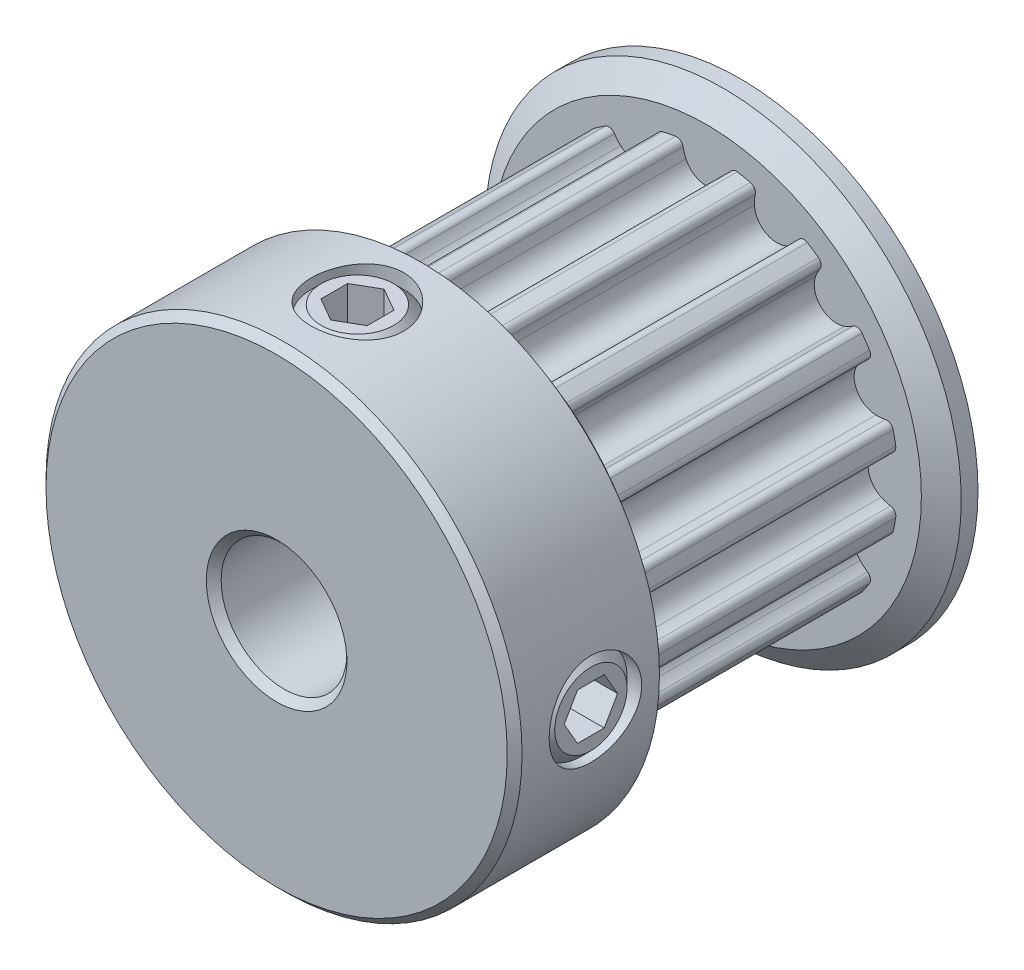
SolidWorks part; units mm, degrees
ref_plane "Front Plane" through (0, 0, 0) normal (0, 0, 1) x (1, 0, 0)
ref_plane "Top Plane" through (0, 0, 0) normal (0, 1, 0) x (1, 0, 0)
ref_plane "Right Plane" through (0, 0, 0) normal (1, 0, 0) x (0, 0, -1)
sketch "Sketch1" plane through (0, 0, 0) normal (0, 0, 1) x (1, 0, 0)
  line L1 (-2.553, 6.1245) -> (2.553, 6.1245) construction
  line L4 (0, 0) -> (0, 6.1245) construction
  line L5 (0, 6.1245) -> (0, 12.0714) construction
  line L6 (0, 7.6455) -> (2.9417, 7.0569) construction
  line L7 (2.9417, 7.0569) -> (3.8741, 6.6682) construction
  line L8 (2.9417, 7.0569) -> (2.553, 6.1245) construction
  line L9 (-2.9417, 7.0569) -> (-2.553, 6.1245) construction
  line L10 (-2.7951, 6.7052) -> (-3.7579, 9.015)
  line L11 (-3.7579, 9.015) -> (3.7579, 9.015)
  line L12 (3.7579, 9.015) -> (2.7951, 6.7052)
  circle A0 centre (0, 0) radius 7.6455 construction
  circle A1 centre (0, 0) radius 9.015 construction
  circle A2 centre (0, 0) radius 7.2645 construction
  arc A3 (-0.7739, 6.6229) -> (0.7739, 6.6229) centre (0, 6.9745) ccw
  arc A4 (-0.7739, 6.6229) -> (-0.8836, 6.9694) centre (0.61, 7.2516) cw
  arc A5 (-2.7951, 6.7052) -> (-1.1695, 7.1697) centre (0, 0) cw
  arc A6 (-0.8836, 6.9694) -> (-1.1695, 7.1697) centre (-1.1292, 6.923) ccw
  arc A7 (2.7951, 6.7052) -> (1.1695, 7.1697) centre (0, 0) ccw
  arc A8 (0.8836, 6.9694) -> (1.1695, 7.1697) centre (1.1292, 6.923) cw
  arc A9 (0.7739, 6.6229) -> (0.8836, 6.9694) centre (-0.61, 7.2516) ccw
  point P6 (0, 20.9083)
  point P11 (0, 7.6455)
  point P13 (0, 9.015)
  point P14 (0, 7.2645)
  dimension "D1" = 8.8369
  dimension "D2" = 4.4259
sketch "Sketch2" plane through (0, 0, 0) normal (1, 0, 0) x (0, 0, -1)
  line L0 (-8.775, 2.3812) -> (8.775, 2.3812)
  line L1 (-8.775, 2.3812) -> (-8.775, 9.015)
  line L2 (-3.29, 9.015) -> (-8.775, 9.015)
  line L3 (-3.925, 2.3813) -> (-3.925, 9.015) construction
  line L4 (-3.925, 9.015) -> (-2.655, 9.015) construction
  line L5 (-2.655, 9.015) -> (-2.655, 7.2645) construction
  line L6 (-2.655, 7.2645) -> (7.505, 7.2645)
  line L7 (7.505, 7.2645) -> (7.505, 9.015) construction
  line L8 (7.505, 9.015) -> (8.775, 9.015) construction
  line L9 (8.775, 9.015) -> (8.775, 2.3812)
  line L10 (-8.775, 0) -> (8.775, 0) construction
  line L11 (8.14, 9.015) -> (7.505, 8.1398)
  line L12 (-2.655, 8.1398) -> (-3.29, 9.015)
  line L14 (-2.655, 8.1398) -> (-2.655, 7.2645)
  line L15 (7.505, 7.2645) -> (7.505, 8.1398)
  line L16 (8.14, 9.015) -> (8.775, 9.015)
  arc A0 (-2.655, 8.1398) -> (-3.29, 9.015) centre (-3.5757, 8.1398) ccw construction
  arc A1 (7.505, 8.1398) -> (8.14, 9.015) centre (8.4257, 8.1398) cw construction
  point P12 (-2.655, 8.1398)
  point P14 (-3.29, 9.015)
  point P20 (7.505, 8.1398)
  point P21 (8.14, 9.015)
  point P25 (7.505, 0)
  point P26 (-2.655, 0)
  dimension "OA" = 17.55
  dimension "Bore" = 4.7625
  dimension "Outside Width" = 11.43
  dimension "Inside Width" = 10.16
revolve "Revolve1" add sketch "Sketch2" angle 360 mid plane about L10
sketch "Sketch3" plane through (0, 0, 0) normal (0, 0, 1) x (1, 0, 0)
  line L6 (3.7579, 9.015) -> (-3.7579, 9.015)
  line L7 (2.7951, 6.7052) -> (3.7579, 9.015)
  line L8 (-3.7579, 9.015) -> (-2.7951, 6.7052)
  line L9 (3.7579, 9.015) -> (-3.7579, 9.015)
  line L10 (2.7951, 6.7052) -> (3.7579, 9.015)
  line L11 (-3.7579, 9.015) -> (-2.7951, 6.7052)
  arc A8 (2.7951, 6.7052) -> (1.1695, 7.1697) centre (0, 0) ccw
  arc A9 (1.1695, 7.1697) -> (0.8836, 6.9694) centre (1.1292, 6.923) ccw
  arc A10 (0.7739, 6.6229) -> (0.8836, 6.9694) centre (-0.61, 7.2516) ccw
  arc A11 (-0.7739, 6.6229) -> (0.7739, 6.6229) centre (0, 6.9745) ccw
  arc A12 (-0.8836, 6.9694) -> (-0.7739, 6.6229) centre (0.61, 7.2516) ccw
  arc A13 (-0.8836, 6.9694) -> (-1.1695, 7.1697) centre (-1.1292, 6.923) ccw
  arc A14 (-1.1695, 7.1697) -> (-2.7951, 6.7052) centre (0, 0) ccw
  arc A15 (2.7951, 6.7052) -> (1.1695, 7.1697) centre (0, 0) ccw
  arc A16 (1.1695, 7.1697) -> (0.8836, 6.9694) centre (1.1292, 6.923) ccw
  arc A17 (0.7739, 6.6229) -> (0.8836, 6.9694) centre (-0.61, 7.2516) ccw
  arc A18 (-0.7739, 6.6229) -> (0.7739, 6.6229) centre (0, 6.9745) ccw
  arc A19 (-0.8836, 6.9694) -> (-0.7739, 6.6229) centre (0.61, 7.2516) ccw
  arc A20 (-0.8836, 6.9694) -> (-1.1695, 7.1697) centre (-1.1292, 6.923) ccw
  arc A21 (-1.1695, 7.1697) -> (-2.7951, 6.7052) centre (0, 0) ccw
  dimension "D1" = 0
extrude "Cut-Extrude1" cut sketch "Sketch3" against normal up to vertex (7.505 mm away) from vertex up to point (0, 7.2645, -7.505) starting at point (0, 7.2645, 2.655)
pattern_circular "CirPattern1" count 16 over 360 about axis through (0, 0, 8.775) along (0, 0, 1) of "Cut-Extrude1"
sketch "Sketch4" plane through (0, 0, 0) normal (1, 0, 0) x (0, -1, 0)
  line L0 (0, -2.655) -> (0, -8.775) construction
  line L1 (-2.3812, -8.775) -> (2.3812, -8.775) construction
  line L2 (8.1398, -2.655) -> (-8.1398, -2.655) construction
  circle A0 centre (0, -5.715) radius 1.7526
extrude "Cut-Extrude2" cut sketch "Sketch4" along normal through all
ref_plane "Plane1" through (0, 0, 5.715) normal (0, 0, 1) x (1, 0, 0)
sketch "Sketch5" plane through (0, 0, 5.715) normal (0, 0, 1) x (1, 0, 0)
  line L0 (0, 0) -> (0, 9.015) construction
  line L1 (2.3812, -1.3716) -> (2.3812, 0)
  line L2 (2.7622, -1.7526) -> (8.462, -1.7526)
  line L3 (2.3812, 0) -> (9.015, 0) construction
  line L4 (2.3812, 0) -> (8.843, 0)
  line L5 (8.843, 0) -> (8.843, -1.3716)
  line L6 (2.7622, -1.7526) -> (2.3812, -1.3716)
  line L7 (8.843, -1.3716) -> (8.462, -1.7526)
  circle A0 centre (0, 0) radius 9.015 construction
  circle A1 centre (0, 0) radius 2.3812 construction
  point P2 (2.3812, -1.7526)
  point P11 (8.843, -1.7526)
revolve "Revolve2" add sketch "Sketch5" angle 360 mid plane about L4
sketch "Sketch6" plane through (8.843, 5.3841, 0) normal (-1, 0, 0) x (0, -1, 0)
  line L1 (5.3841, 6.7269) -> (4.5078, 6.2209)
  line L2 (4.5078, 6.2209) -> (4.5078, 5.2091)
  line L3 (4.5078, 5.2091) -> (5.3841, 4.7031)
  line L4 (5.3841, 4.7031) -> (6.2604, 5.2091)
  line L5 (6.2604, 5.2091) -> (6.2604, 6.2209)
  line L6 (6.2604, 6.2209) -> (5.3841, 6.7269)
  circle A0 centre (5.3841, 5.715) radius 0.8763 construction
  dimension "D1" = 1.7526
extrude "Cut-Extrude3" cut sketch "Sketch6" along normal blind 1.3144
pattern_circular "CirPattern3" count 2 over 90 about axis through (0, 0, 8.775) along (0, 0, 1) of "Cut-Extrude2", "Revolve2", "Cut-Extrude3"
chamfer "Chamfer1" distance 0.2807 angle 45 2 edges at (2.3812, 0, 8.775) (9.015, 0, 8.775)
ref_axis "Center Axis 1" through (0, 0, -8.775) along (0, 0, 1)
ref_plane "Contact Plane 1" through (0, 0, 8.775) normal (0, 0, 1) x (1, 0, 0)
ref_plane "Contact Plane 2" through (0, 0, -8.775) normal (0, 0, -1) x (-1, 0, 0)
equation "\"D2@Sketch1\"= \"D1@Sketch1\" / 2"
equation "\"D1@Sketch6\" = \"Set Screw@Sketch4\" / 2"
equation "\"D1@Cut-Extrude3\" = \"D1@Sketch6\"*.75"
